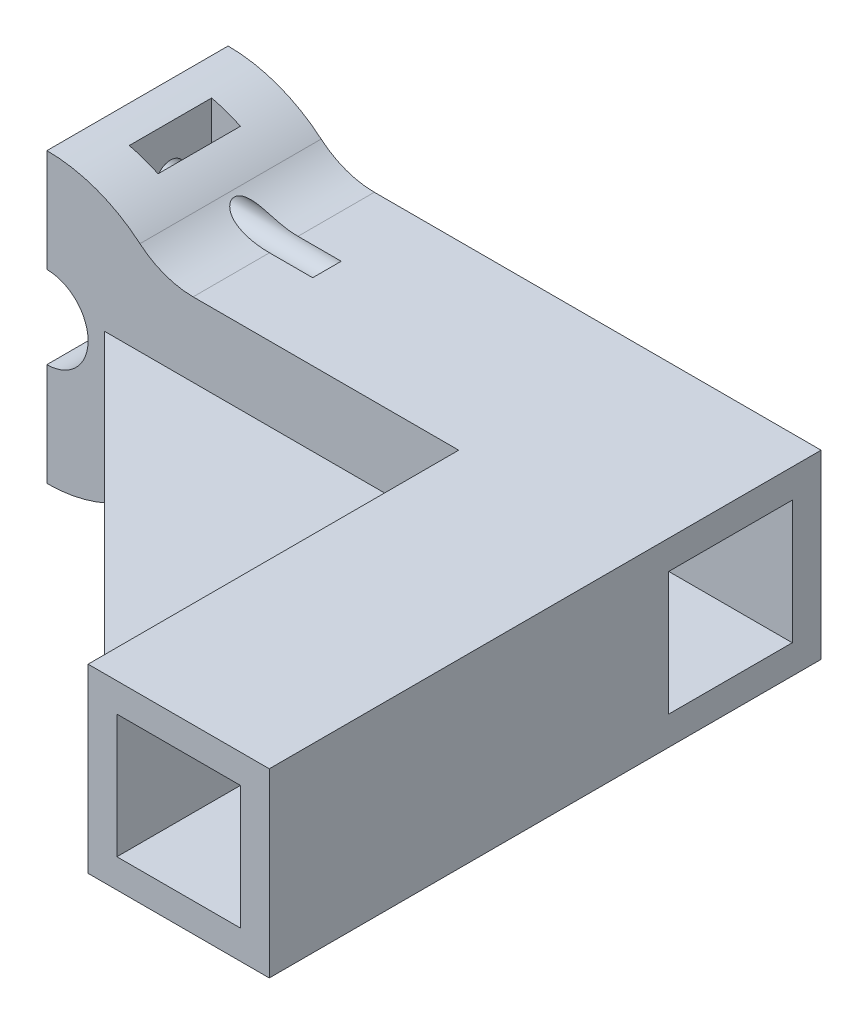
SolidWorks part; units mm, degrees
ref_plane "Front Plane" through (0, 0, 0) normal (0, 0, 1) x (1, 0, 0)
ref_plane "Top Plane" through (0, 0, 0) normal (0, 1, 0) x (1, 0, 0)
ref_plane "Right Plane" through (0, 0, 0) normal (1, 0, 0) x (0, 0, -1)
sketch "Sketch1" plane through (0, 0, 0) normal (0, 0, 1) x (1, 0, 0)
  line L0 (41.5599, 4.1233) -> (41.5599, -17.8767) construction
  line L1 (5.1706, 4.1233) -> (63.5599, 4.1233)
  line L2 (-8.4401, 7.6443) -> (-8.4401, -1.8767)
  line L3 (5.1706, -17.8767) -> (63.5599, -17.8767)
  line L4 (63.5599, 4.1233) -> (63.5599, -17.8767)
  line L5 (-8.4401, -11.8767) -> (-8.4401, -14.3557)
  line L6 (-8.4401, -14.3557) -> (-8.4401, -24.3767)
  line L7 (-8.4401, 7.6443) -> (-8.4401, 10.6233)
  arc A0 (-8.4401, -11.8767) -> (-8.4401, -1.8767) centre (-8.4401, -6.8767) ccw
  arc A1 (5.1706, 4.1233) -> (-8.4401, 10.6233) centre (-8.4401, -6.8767) ccw
  arc A2 (-8.4401, -24.3767) -> (5.1706, -17.8767) centre (-8.4401, -6.8767) ccw
  dimension "D4" = 10
  dimension "D5" = 35
  dimension "D1" = 22
  dimension "D2" = 50
  dimension "D3" = 22
  dimension "D6" = 11
extrude "Boss-Extrude1" add sketch "Sketch1" along normal blind 22
sketch "Sketch2" plane through (0, 0, 22) normal (0, 0, 1) x (1, 0, 0)
  line L0 (5.1706, -17.8767) -> (63.5599, -17.8767) construction
  line L1 (63.5599, 4.1233) -> (41.5599, 4.1233)
  line L2 (63.5599, 4.1233) -> (63.5599, -17.8767)
  line L3 (63.5599, -17.8767) -> (41.5599, -17.8767)
  line L4 (41.5599, 4.1233) -> (41.5599, -17.8767)
  dimension "D1" = 22
extrude "Boss-Extrude2" add sketch "Sketch2" along normal blind 45
sketch "Sketch3" plane through (0, 0, 67) normal (0, 0, 1) x (1, 0, 0)
  line L0 (63.5599, -17.8767) -> (63.5599, 4.1233) construction
  line L1 (45.0599, 0.6233) -> (60.0599, 0.6233)
  line L2 (45.0599, 0.6233) -> (45.0599, -14.3767)
  line L3 (45.0599, -14.3767) -> (60.0599, -14.3767)
  line L4 (60.0599, 0.6233) -> (60.0599, -14.3767)
  line L5 (63.5599, 4.1233) -> (41.5599, 4.1233) construction
  dimension "D1" = 15
  dimension "D2" = 3.5
  dimension "D3" = 15
  dimension "D4" = 3.5
extrude "Cut-Extrude1" cut sketch "Sketch3" against normal offset from surface (43 mm away) 2 up to face at (8.2716, -5.5017, 22)
sketch "Sketch4" plane through (63.5599, 0, 0) normal (1, 0, 0) x (0, 0, -1)
  line L0 (-67, 4.1233) -> (0, 4.1233) construction
  line L1 (-3.5, 0.6233) -> (-18.5, 0.6233)
  line L2 (-3.5, 0.6233) -> (-3.5, -14.3767)
  line L3 (-3.5, -14.3767) -> (-18.5, -14.3767)
  line L4 (-18.5, 0.6233) -> (-18.5, -14.3767)
  line L5 (0, -17.8767) -> (0, 4.1233) construction
  dimension "D1" = 15
  dimension "D2" = 15
  dimension "D3" = 3.5
  dimension "D4" = 3.5
extrude "Cut-Extrude2" cut sketch "Sketch4" against normal blind 45
ref_plane "Plane1" through (0, -6.8767, 0) normal (0, 1, 0) x (1, 0, 0)
sketch "Sketch6" plane through (0, -6.8767, 0) normal (0, 1, 0) x (1, 0, 0)
  line L0 (-1.4401, -22) -> (41.5599, -65)
  line L1 (41.5599, -22) -> (5.1706, -22) construction
  line L2 (41.5599, -67) -> (41.5599, -22) construction
  line L3 (41.5599, -65) -> (41.5599, -22)
  line L4 (41.5599, -22) -> (-1.4401, -22)
  line L5 (-3.4401, -22) -> (-3.4401, 0) construction
  dimension "D1" = 2
  dimension "D2" = 45
extrude "Boss-Extrude3" add sketch "Sketch6" along normal blind 2 and the other way blind 2
fillet "Fillet1" radius 10 2 edges at (5.1706, -17.8767, 11) (5.1706, 4.1233, 11)
sketch "Sketch5" plane through (-8.4401, 0, 0) normal (-1, 0, 0) x (0, 0, 1)
  line L0 (0, 4.3733) -> (22, 4.3733) construction
  line L1 (0, 10.6233) -> (0, -1.8767) construction
  line L2 (22, 10.6233) -> (22, -1.8767) construction
  line L3 (0, -18.1267) -> (22, -18.1267) construction
  line L4 (0, -11.8767) -> (0, -24.3767) construction
  line L5 (22, -11.8767) -> (22, -24.3767) construction
  circle A1 centre (11, 4.3733) radius 1.75
  circle A3 centre (11, -18.1267) radius 1.75
  dimension "D1" = 3.5
  dimension "D4" = 11
  dimension "D5" = 11
extrude "Cut-Extrude3" cut sketch "Sketch5" against normal blind 23
sketch "Sketch7" plane through (0, 4.1233, 0) normal (0, 1, 0) x (1, 0, 0)
  line L1 (14.5599, -9.2679) -> (14.5599, -12.7321) construction
  line L2 (-4.4401, -6) -> (-0.9401, -6)
  line L3 (-4.4401, -6) -> (-4.4401, -16)
  line L4 (-4.4401, -16) -> (-0.9401, -16)
  line L5 (-0.9401, -6) -> (-0.9401, -16)
  line L7 (-8.4401, -22) -> (-8.4401, 0) construction
  point P0 (14.5599, -11)
  dimension "D1" = 10
  dimension "D2" = 5
  dimension "D3" = 4
  dimension "D4" = 3.5
extrude "Cut-Extrude4" cut sketch "Sketch7" against normal blind 4 and the other way blind 37
mirror "Mirror1" about plane through (0, -6.8767, 0) normal (0, 1, 0) of "Cut-Extrude4"
